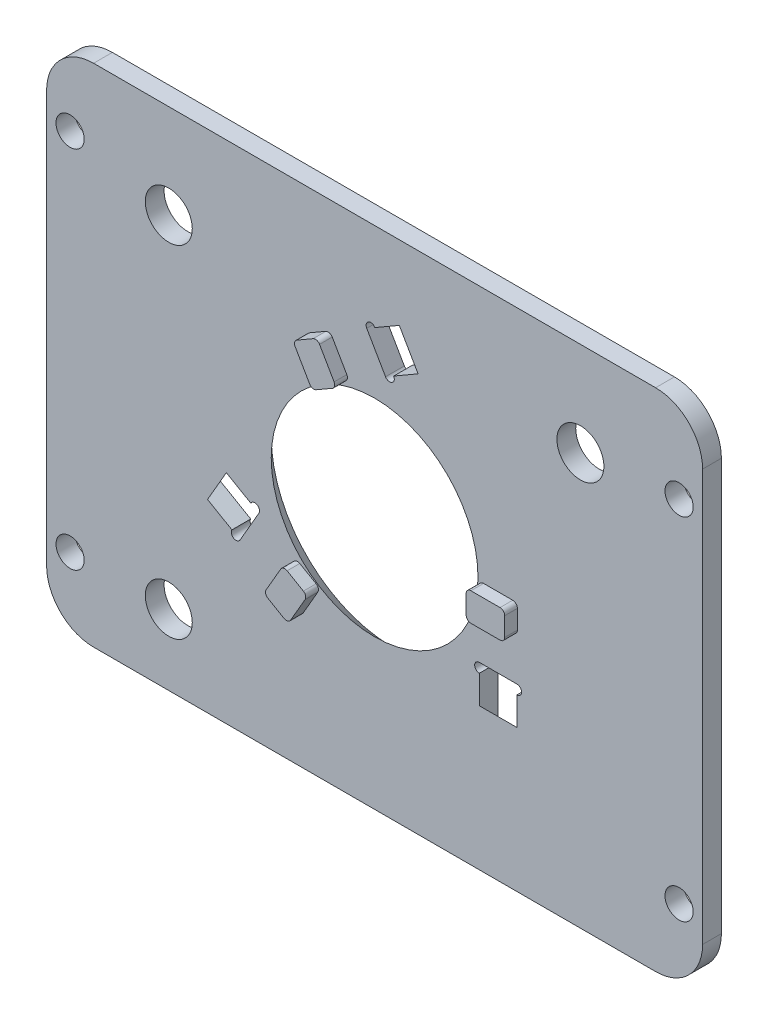
SolidWorks part; units mm, degrees
note: The reader was unsure of these and kept them because the rebuilt part matched: shared geometry of "草圖1<3>".
ref_plane "前基準面" through (0, 0, 0) normal (0, 0, 1) x (1, 0, 0)
ref_plane "上基準面" through (0, 0, 0) normal (0, 1, 0) x (1, 0, 0)
ref_plane "右基準面" through (0, 0, 0) normal (1, 0, 0) x (0, 0, -1)
sketch "草圖1" plane through (0, 0, 0) normal (0, 0, 1) x (1, 0, 0)
  line L0 (38, 0) -> (0, 0) construction
  line L1 (-38, 30) -> (38, 30)
  line L2 (-38, 30) -> (-38, -30)
  line L3 (-38, -30) -> (38, -30)
  line L4 (38, 30) -> (38, -30)
  line L5 (-38, 30) -> (38, -30) construction
  line L6 (-38, -30) -> (38, 30) construction
  line L7 (14.6965, -0.2805) -> (11.5965, -0.2805)
  line L8 (11.0965, -0.7805) -> (11.0965, -2.7805)
  line L9 (11.5965, -3.2805) -> (14.6965, -3.2805)
  line L10 (15.1965, -2.7805) -> (15.1965, -0.7805)
  line L11 (13.1465, -0.2805) -> (13.1465, -3.2805) construction
  line L12 (15.1965, -1.7805) -> (11.0965, -1.7805) construction
  line L13 (13.1465, -1.7805) -> (15.1965, -0.2805) construction
  line L14 (-7.5929, -12.5903) -> (-6.0429, -9.9057)
  line L15 (-6.2259, -9.2226) -> (-7.958, -8.2226)
  line L16 (-8.641, -8.4057) -> (-10.191, -11.0903)
  line L17 (-10.008, -11.7733) -> (-8.2759, -12.7733)
  line L18 (-9.1419, -12.2733) -> (-7.0919, -8.7226) construction
  line L19 (-6.8179, -11.248) -> (-9.416, -9.748) construction
  line L20 (-8.1169, -10.498) -> (-7.8429, -13.0233) construction
  line L28 (13.1465, -0.2805) -> (13.1465, -18.1491) construction
  line L31 (11.1465, -7.7805) -> (15.1465, -7.7805)
  line L32 (11.1465, -7.7805) -> (11.1465, -8.7805)
  line L33 (11.1465, -8.7805) -> (15.1465, -8.7805)
  line L34 (15.1465, -7.7805) -> (15.1465, -8.7805)
  line L35 (11.1465, -7.7805) -> (15.1465, -8.7805) construction
  line L36 (11.1465, -8.7805) -> (15.1465, -7.7805) construction
  line L37 (-8.1169, -10.498) -> (2.341, -16.5359) construction
  line L42 (-9.416, -9.748) -> (-17.2102, -5.248) construction
  line L43 (-6.575, 11.3882) -> (-6.0892, 11.6687) construction
  line L44 (-7.1071, 12.8708) -> (-5.5571, 10.1861)
  line L49 (-6.9241, 13.5538) -> (-5.192, 14.5538)
  line L50 (-15.1791, -8.73) -> (-13.1791, -5.2659)
  line L51 (-14.3131, -9.23) -> (-15.1791, -8.73)
  line L52 (-12.3131, -5.7659) -> (-14.3131, -9.23)
  line L53 (-13.1791, -5.2659) -> (-12.3131, -5.7659)
  line L54 (-12.7461, -5.5159) -> (-14.7461, -8.98) construction
  line L55 (-4.509, 14.3708) -> (-2.959, 11.6861)
  line L60 (0, 0) -> (-15.5652, 26.9597) construction
  line L61 (-3.142, 11.0031) -> (-4.8741, 10.0031)
  line L62 (0, 0) -> (-12.3219, -21.3421) construction
  line L63 (-6.0581, 14.0538) -> (-4.0081, 10.5031) construction
  line L64 (-7.3571, 13.3038) -> (-5.0331, 12.2785) construction
  line L65 (-5.0331, 12.2785) -> (-5.3071, 9.7531) construction
  line L66 (-4.759, 14.8038) -> (-5.0331, 12.2785) construction
  line L67 (-5.0331, 12.2785) -> (-2.709, 11.2531) construction
  line L68 (-6.575, 11.3882) -> (6.9012, 19.1687) construction
  line L69 (-0.8369, 17.0105) -> (1.1631, 13.5464)
  line L70 (-0.8369, 17.0105) -> (0.0291, 17.5105)
  line L71 (0.0291, 17.5105) -> (2.0291, 14.0464)
  line L72 (2.0291, 14.0464) -> (1.1631, 13.5464)
  line L73 (-0.4039, 17.2605) -> (1.5961, 13.7964) construction
  circle A4 centre (13.1465, -0.9905) radius 0.15 construction
  circle A9 centre (-7.4328, -10.893) radius 0.15 construction
  circle A18 centre (11.1465, -8.2805) radius 0.5
  circle A19 centre (15.1465, -8.2805) radius 0.5
  circle A20 centre (-12.7461, -5.5159) radius 0.5
  circle A21 centre (-14.7461, -8.98) radius 0.5
  circle A33 centre (-0.4039, 17.2605) radius 0.5
  circle A34 centre (1.5961, 13.7964) radius 0.5
  arc A35 (11.0965, -2.7805) -> (11.5965, -3.2805) centre (11.5965, -2.7805) ccw
  arc A36 (14.6965, -3.2805) -> (15.1965, -2.7805) centre (14.6965, -2.7805) ccw
  arc A37 (14.6965, -0.2805) -> (15.1965, -0.7805) centre (14.6965, -0.7805) cw
  arc A38 (11.5965, -0.2805) -> (11.0965, -0.7805) centre (11.5965, -0.7805) ccw
  arc A39 (-7.958, -8.2226) -> (-8.641, -8.4057) centre (-8.208, -8.6557) ccw
  arc A40 (-6.0429, -9.9057) -> (-6.2259, -9.2226) centre (-6.4759, -9.6557) ccw
  arc A41 (-10.191, -11.0903) -> (-10.008, -11.7733) centre (-9.758, -11.3403) ccw
  arc A42 (-7.5929, -12.5903) -> (-8.2759, -12.7733) centre (-8.0259, -12.3403) cw
  arc A43 (-5.192, 14.5538) -> (-4.509, 14.3708) centre (-4.942, 14.1208) cw
  arc A44 (-2.959, 11.6861) -> (-3.142, 11.0031) centre (-3.392, 11.4361) cw
  arc A45 (-5.5571, 10.1861) -> (-4.8741, 10.0031) centre (-5.1241, 10.4361) ccw
  arc A46 (-7.1071, 12.8708) -> (-6.9241, 13.5538) centre (-6.6741, 13.1208) cw
  point P0 (0, 0)
  point P20 (11.0965, -3.2805)
  point P28 (38, 0)
  point P29 (13.1465, -8.2805)
  point P42 (-13.3131, -7.498)
  point P44 (11.0965, -0.2805)
  point P52 (-6.3321, 11.5285)
  point P58 (0.0072, -0.0003)
  point P60 (-5.7929, -9.4726)
  point P63 (-10.441, -11.5233)
  point P69 (0.1631, 15.2785)
  point P70 (0.055, -0.0317)
  point P120 (-8.1169, -10.498)
  dimension "D5" = 0.561
  dimension "D6" = 0.3
  dimension "D11" = 4.1
  dimension "D12" = 5
  dimension "D10" = 13.15
  dimension "D25" = 0.5
  dimension "D29" = 90
  dimension "D23" = 4.1
  dimension "D32" = 0.3
  dimension "D34" = 13.15
  dimension "D35" = 4
  dimension "D36" = 1
  dimension "D18" = 3
  dimension "D20" = 0.561
  dimension "D21" = 0.5
  dimension "D1" = 76
  dimension "D2" = 60
  dimension "D3" = 4.1
  dimension "D4" = 3
  dimension "D7" = 0.79
  dimension "D8" = 38
  dimension "D9" = 13.1465
  dimension "D13" = 2
  dimension "D14" = 1
  dimension "D15" = 4
  dimension "D16" = 1
  dimension "D17" = 5
  dimension "D19" = 0.561
  dimension "D22" = 120
  dimension "D24" = 120
  dimension "D30" = 0
  dimension "D31" = 3
  dimension "D33" = 0.79
  dimension "D38" = 5
extrude "填料-伸長1" add sketch "草圖1" along normal blind 2
extrude "填料-伸長2" add sketch "草圖1<3>" along normal blind 3.35
sketch "草圖1<3>" plane through (0, 0, 0) normal (0, 0, 1) x (1, 0, 0) same geometry as "草圖1"
sketch "草圖2" plane through (0, 0, 0) normal (0, 0, -1) x (-1, 0, 0)
  line L0 (-29.9, 26.9043) -> (29.9, 26.9043)
  line L1 (34.9, 21.9043) -> (34.9, -21.9)
  line L2 (29.9, -26.9) -> (-29.9, -26.9)
  line L3 (-34.9, -21.9) -> (-34.9, 21.9043)
  line L4 (38, 30) -> (-38, 30) construction
  line L5 (-38, 30) -> (-38, -30) construction
  line L6 (38, -30) -> (-38, -30) construction
  line L7 (38, 30) -> (38, -30) construction
  arc A0 (-29.9, -26.9) -> (-34.9, -21.9) centre (-29.9, -21.9) cw
  arc A1 (34.9, -21.9) -> (29.9, -26.9) centre (29.9, -21.9) cw
  arc A2 (29.9, 26.9043) -> (34.9, 21.9043) centre (29.9, 21.9043) cw
  arc A3 (-29.9, 26.9043) -> (-34.9, 21.9043) centre (-29.9, 21.9043) ccw
  line M5 (-38, 30) -> (-38, -30)
  line M6 (-38, -30) -> (38, -30)
  line M7 (38, -30) -> (38, 30)
  line M8 (38, 30) -> (-38, 30)
  dimension "D5" = 5
  dimension "D1" = 3.1
  dimension "D2" = 3.0957
  dimension "D3" = 3.1
  dimension "D4" = 3.1
extrude "除料-伸長1" cut sketch "草圖2" against normal blind 2.95 contours A3 L0 A2 L1 A1 L2 A0 L3 M8 M5 M6 M7
sketch "草圖3" plane through (0, 0, 0) normal (0, 0, -1) x (-1, 0, 0)
  circle A0 centre (0, 0) radius 1.715
  dimension "D1" = 3.43
extrude "除料-伸長2" cut sketch "草圖3" against normal blind 10
sketch "草圖4" plane through (0, 0, 0) normal (0, 1, 0) x (1, 0, 0)
  line L0 (0, 2.8971) -> (0, -5.2292) construction
  line L1 (0, -2) -> (11, -2)
  line L2 (-29.9, -2) -> (29.9, -2) construction
  line L3 (11, -2) -> (13, 0)
  line L4 (29.9, 0) -> (-29.9, 0) construction
  line L5 (13, 0) -> (0, 0)
  line L6 (0, 0) -> (0, -2)
  dimension "D1" = 11
  dimension "D2" = 13
revolve "除料-旋轉1" cut sketch "草圖4" angle 360 about L0
sketch "草圖5" plane through (0, 0, 0) normal (0, 0, 1) x (1, 0, 0)
  line L0 (34.9, 21.9043) -> (24.9, 21.9043) construction
  line L1 (24.9, 21.9043) -> (24.9, -21.9) construction
  line L2 (24.9, -21.9) -> (34.9, -21.9) construction
  line L3 (34.9, -21.9) -> (34.9, 21.9043) construction
  line L4 (-34.9, -21.9) -> (-34.9, 21.9043) construction
  line L5 (-34.9, 0.0022) -> (34.9, 0.0022) construction
  line L6 (0, 26.9043) -> (0, -26.9) construction
  line L7 (-29.9, 26.9043) -> (29.9, 26.9043) construction
  line L8 (29.9, -26.9) -> (-29.9, -26.9) construction
  circle A0 centre (32.4, 17.9043) radius 1.5
  circle A1 centre (-32.4, 19.4043) radius 1.5
  circle A2 centre (-32.4, -19.4) radius 1.5
  circle A3 centre (32.4, -19.4) radius 1.5
  dimension "D2" = 3
  dimension "D5" = 3
  dimension "D1" = 10
  dimension "D3" = 2.5
  dimension "D4" = 4
  dimension "D6" = 2.5
  dimension "D7" = 2.5
extrude "除料-伸長3" cut sketch "草圖5" along normal through all
sketch "草圖6" plane through (0, 0, 2) normal (0, 0, 1) x (1, 0, 0)
  line L0 (-29.9, 26.9043) -> (29.9, 26.9043) construction
  line L1 (-34.9, -21.9) -> (-34.9, 21.9043) construction
  line L2 (0, 26.9043) -> (0, -26.9) construction
  line L3 (29.9, -26.9) -> (-29.9, -26.9) construction
  circle A0 centre (-21.9, 16.9043) radius 2.5
  circle A1 centre (21.9, 16.9043) radius 2.5
  circle A2 centre (-21.9, -19.4) radius 2.5
  dimension "D3" = 5
  dimension "D4" = 5
  dimension "D1" = 10
  dimension "D2" = 13
  dimension "D5" = 7.5
extrude "除料-伸長4" cut sketch "草圖6" against normal through all
ref_plane "平面1" through (11.1465, 0, 0) normal (-1, 0, 0) x (0, 0, 1)
sketch "草圖7" plane through (11.1465, 0, 0) normal (-1, 0, 0) x (0, 0, 1)
  line L10 (2, -8.7805) -> (2, -11.7805)
  line L11 (2, -12.5903) -> (2, -9.9057) construction
  line L12 (2, -11.7805) -> (0, -13.7805)
  line L13 (0, 21.9043) -> (0, -21.9) construction
  line L14 (0, -7.7805) -> (0, -8.7805)
  line L15 (2, -7.7805) -> (0, -7.7805)
  line L16 (2, -8.7805) -> (2, -7.7805)
  line L17 (0, -8.7805) -> (2, -8.7805)
  line L18 (0, -7.7805) -> (0, -8.7805) construction
  line L19 (2, -7.7805) -> (0, -7.7805) construction
  line L20 (2, -8.7805) -> (2, -7.7805) construction
  line L21 (0, -8.7805) -> (2, -8.7805) construction
  line L22 (0, -13.7805) -> (0, -8.7805)
  line L23 (0, -8.7805) -> (2, -8.7805)
  dimension "D1" = 0
  dimension "D2" = 3
  dimension "D3" = 5
extrude "除料-伸長5" cut sketch "草圖7" against normal blind 4
ref_plane "平面2" through (-5.575, -9.6562, 0) normal (0.5, 0.866, 0) x (0.866, -0.5, 0)
sketch "草圖8" plane through (-5.575, -9.6562, 0) normal (0.5, 0.866, 0) x (0.866, -0.5, 0)
  line L9 (-8.7805, -2) -> (-8.7805, 0)
  line L10 (-8.7805, 0) -> (-13.7805, 0)
  line L11 (12.442, 0) -> (-39.3463, 0) construction
  line L12 (-13.7805, 0) -> (-11.7805, -2)
  line L13 (-7.7805, 0) -> (-8.7805, 0)
  line L14 (-7.7805, -2) -> (-7.7805, 0)
  line L15 (-8.7805, -2) -> (-7.7805, -2)
  line L16 (-8.7805, 0) -> (-8.7805, -2)
  line L17 (-7.7805, 0) -> (-8.7805, 0) construction
  line L18 (-7.7805, -2) -> (-7.7805, 0) construction
  line L19 (-8.7805, -2) -> (-7.7805, -2) construction
  line L20 (-8.7805, 0) -> (-8.7805, -2) construction
  line L21 (-39.3463, -2) -> (12.442, -2) construction
  line L22 (-11.7805, -2) -> (-8.7805, -2)
  dimension "D1" = 0
  dimension "D2" = 5
  dimension "D3" = 3
extrude "除料-伸長6" cut sketch "草圖8" against normal blind 4
ref_plane "平面3" through (-5.575, 9.6562, 0) normal (0.5, -0.866, 0) x (-0.866, -0.5, 0)
sketch "草圖9" plane through (-5.575, 9.6562, 0) normal (0.5, -0.866, 0) x (-0.866, -0.5, 0)
  line L4 (-7.7805, 0) -> (-8.7805, 0)
  line L5 (-7.7805, -2) -> (-7.7805, 0)
  line L6 (-8.7805, -2) -> (-7.7805, -2)
  line L7 (-8.7805, 0) -> (-8.7805, -2)
  line L8 (-7.7805, 0) -> (-8.7805, 0) construction
  line L9 (-7.7805, -2) -> (-7.7805, 0) construction
  line L10 (-8.7805, -2) -> (-7.7805, -2) construction
  line L11 (-8.7805, 0) -> (-8.7805, -2) construction
  line L14 (-8.7805, -2) -> (-8.7805, 0)
  line L15 (-8.7805, 0) -> (-13.7805, 0)
  line L16 (-16.8592, 0) -> (-19.8592, 0) construction
  line L17 (-13.7805, 0) -> (-11.7805, -2)
  line L18 (-19.2743, -2) -> (-12.4442, -2) construction
  line L19 (-11.7805, -2) -> (-8.7805, -2)
  dimension "D2" = 3
  dimension "D3" = 5
  dimension "D1" = 0
extrude "除料-伸長7" cut sketch "草圖9" against normal blind 4
